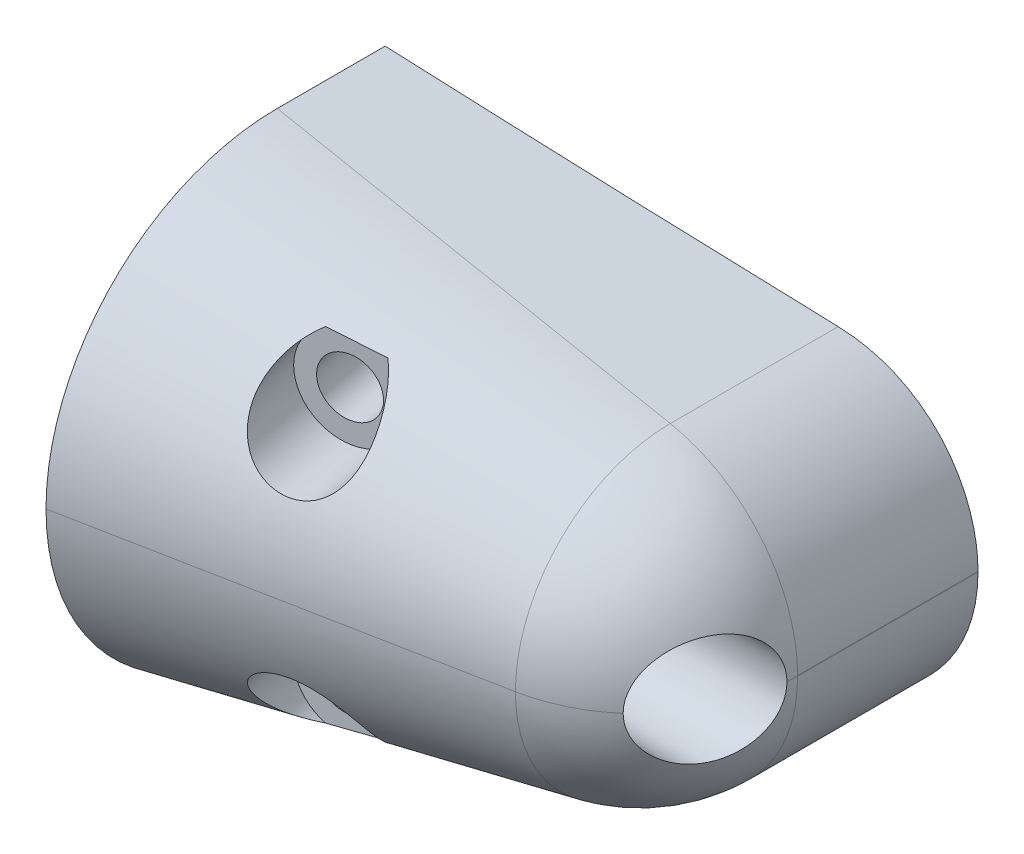
SolidWorks part; units mm, degrees
ref_plane "Plan de face" through (0, 0, 0) normal (0, 0, 1) x (1, 0, 0)
ref_plane "Plan de dessus" through (0, 0, 0) normal (0, 1, 0) x (1, 0, 0)
ref_plane "Plan de droite" through (0, 0, 0) normal (1, 0, 0) x (0, 0, -1)
sketch "Esquisse1" plane through (0, 0, 0) normal (0, 0, 1) x (1, 0, 0)
  line L1 (0, -6) -> (20, -6)
  line L2 (0, -6) -> (0, 12)
  line L3 (0, 12) -> (20, 12)
  line L4 (20, -6) -> (20, 12)
  dimension "D1" = 20
  dimension "D2" = 18
extrude "Boss.-Extru.1" add sketch "Esquisse1" along normal blind 17
sketch "Esquisse2" plane through (0, 12, 0) normal (0, 1, 0) x (1, 0, 0)
  line L0 (20.0456, -0.0409) -> (0, -3.849)
  line L1 (0, -17) -> (0, 0) construction
  line L2 (0, -3.849) -> (0, 0)
extrude "Enlèv. mat.-Extru.1" cut sketch "Esquisse2" against normal through all and the other way through all flip side to cut
sketch "Esquisse4" plane through (0.7057, 0, 3.715) normal (-0.1866, 0, -0.9824) x (-0.9824, 0, 0.1866)
  line L0 (-19.6393, -6) -> (-19.6393, 12) construction
  line L1 (-19.6393, 11.9) -> (3.1728, 11.9)
  line L2 (-19.6393, 11.9) -> (-19.6393, -5.9)
  line L3 (-19.6393, -5.9) -> (3.1728, -5.9)
  line L4 (3.1728, 11.9) -> (3.1728, -5.9)
  line L6 (-19.6393, 12) -> (0.7184, 12) construction
  line L7 (0.7184, -6) -> (-19.6393, -6) construction
  line L8 (3.1728, 12) -> (3.1728, -6) construction
  dimension "D1" = 0
  dimension "D2" = 0
  dimension "D3" = 0.1
  dimension "D4" = 0.1
extrude "Enlèv. mat.-Extru.3" cut sketch "Esquisse4" against normal blind 1
ref_plane "Plan2" through (3.8137, 0, 20.075) normal (-0.1866, 0, -0.9824) x (-0.9824, 0, 0.1866)
fillet "Congé2" radius 40 2 edges at (10, 11.9, 2.9672) (10, -5.9, 2.9672)
sketch "Esquisse5" plane through (0, 0, 0) normal (-1, 0, 0) x (0, 0, 1)
  line L0 (17, 12) -> (3.849, 12) construction
  line L1 (17, -6) -> (3.849, -6) construction
  line L2 (17, 12) -> (17, -6) construction
  circle A0 centre (10.5, 3) radius 2.1
  dimension "D1" = 9
  dimension "D2" = 9
  dimension "D3" = 6.5
extrude "Enlèv. mat.-Extru.4" cut sketch "Esquisse5" against normal through all
fillet "Congé3" radius 9 2 edges at (10, 12, 17) (10, -6, 17)
chamfer "Chanfrein1" distance 4 angle 79 4 edges at (20, -6, 4.0248) (20, -3.364, 14.364) (20, 9.364, 14.364) (20, 12, 4.0248)
fillet "Congé4" radius 6.05 4 edges at (20, -2, 4.3748) (20, -0.5355, 11.5355) (20, 6.5355, 11.5355) (20, 8, 4.3748)
sketch "Esquisse6" plane through (247.8041, 0, -26.2768) normal (-0.1866, 0, -0.9824) x (-0.9824, 0, 0.1866)
  circle A0 centre (244, 7.9) radius 1.1
  circle A1 centre (244, -1.9) radius 1.1
  point P2 (0, 0)
  point P3 (0, 0)
  point P6 (0, 0)
  point P7 (0, 0)
  point P8 (0, 0)
  point P9 (0, 0)
  point P10 (0, 0)
  point P11 (0, 0)
  point P12 (0, 0)
  point P13 (0, 0)
  point P14 (0, 0)
  point P15 (0, 0)
  point P16 (0, 0)
  point P17 (0, 0)
  point P18 (0, 0)
  point P19 (0, 0)
  point P20 (0, 0)
extrude "Enlèv. mat.-Extru.5" cut sketch "Esquisse6" along normal through all
sketch "Esquisse10" plane through (3.8137, 0, 20.075) normal (-0.1866, 0, -0.9824) x (-0.9824, 0, 0.1866)
  circle A0 centre (-4.4, 7.9) radius 1.9
  circle A1 centre (-4.4, -1.9) radius 1.9
  point P4 (0, 0)
  point P5 (0, 0)
  point P6 (0, 0)
  point P7 (0, 0)
  point P8 (0, 0)
  point P9 (0, 0)
  point P10 (0, 0)
  point P11 (0, 0)
extrude "Enlèv. mat.-Extru.6" cut sketch "Esquisse10" along normal blind 7.5
